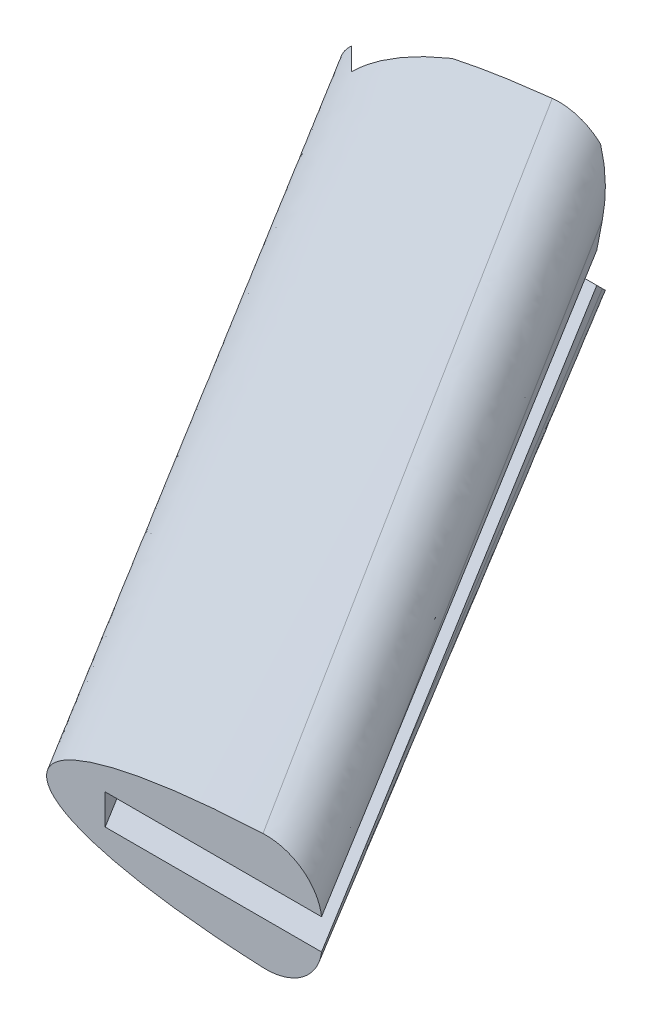
SolidWorks part; units mm, degrees
ref_plane "Front Plane" through (0, 0, 0) normal (0, 0, 1) x (1, 0, 0)
ref_plane "Top Plane" through (0, 0, 0) normal (0, 1, 0) x (1, 0, 0)
ref_plane "Right Plane" through (0, 0, 0) normal (1, 0, 0) x (0, 0, -1)
ref_plane "Plane1" through (0, 0, 82.55) normal (0, 0, 1) x (1, 0, 0)
curve "Curve1"
  spline degree 3 poles (25.4, 0.032, 0) (25.3951, 0.0327, 0) (25.3753, 0.0355, 0) (25.3309, 0.0417, 0) (25.257, 0.052, 0) (25.1537, 0.0664, 0) (25.0214, 0.0846, 0) (24.8603, 0.1068, 0) (24.6708, 0.1326, 0) (24.4533, 0.1619, 0) (24.2084, 0.1946, 0) (23.9366, 0.2304, 0) (23.6385, 0.2691, 0) (23.3149, 0.3106, 0) (22.9666, 0.3545, 0) (22.5942, 0.4008, 0) (22.1987, 0.449, 0) (21.7811, 0.499, 0) (21.3422, 0.5505, 0) (20.8832, 0.6032, 0) (20.405, 0.6571, 0) (19.9089, 0.7116, 0) (19.3959, 0.7667, 0) (18.8673, 0.8219, 0) (18.3242, 0.8772, 0) (17.7681, 0.9321, 0) (17.2001, 0.9864, 0) (16.6216, 1.0399, 0) (16.0339, 1.0922, 0) (15.4384, 1.143, 0) (14.8366, 1.1921, 0) (14.2297, 1.2391, 0) (13.6193, 1.2836, 0) (13.0067, 1.3254, 0) (12.3935, 1.3642, 0) (11.7809, 1.3995, 0) (11.1705, 1.4311, 0) (10.5636, 1.4587, 0) (9.9618, 1.4818, 0) (9.3663, 1.5004, 0) (8.7786, 1.514, 0) (8.2001, 1.5224, 0) (7.632, 1.5254, 0) (7.0758, 1.5227, 0) (6.5327, 1.5144, 0) (6.0041, 1.5, 0) (5.491, 1.4798, 0) (4.9948, 1.4535, 0) (4.5166, 1.4212, 0) (4.0575, 1.3829, 0) (3.6185, 1.3388, 0) (3.2008, 1.2888, 0) (2.8052, 1.2334, 0) (2.4327, 1.1725, 0) (2.0841, 1.1064, 0) (1.7603, 1.0355, 0) (1.462, 0.96, 0) (1.1898, 0.8801, 0) (0.9445, 0.7962, 0) (0.7264, 0.7086, 0) (0.536, 0.6175, 0) (0.3737, 0.523, 0) (0.2396, 0.4254, 0) (0.1341, 0.3245, 0) (0.0574, 0.22, 0) (0.0105, 0.1114, 0) (-0.0051, 0, 0) (0.0105, -0.1114, 0) (0.0574, -0.22, 0) (0.1341, -0.3245, 0) (0.2396, -0.4254, 0) (0.3737, -0.523, 0) (0.536, -0.6175, 0) (0.7264, -0.7086, 0) (0.9445, -0.7962, 0) (1.1898, -0.8801, 0) (1.462, -0.96, 0) (1.7603, -1.0355, 0) (2.0841, -1.1064, 0) (2.4327, -1.1725, 0) (2.8052, -1.2334, 0) (3.2008, -1.2888, 0) (3.6185, -1.3388, 0) (4.0575, -1.3829, 0) (4.5166, -1.4212, 0) (4.9948, -1.4535, 0) (5.491, -1.4798, 0) (6.0041, -1.5, 0) (6.5327, -1.5144, 0) (7.0758, -1.5227, 0) (7.632, -1.5254, 0) (8.2001, -1.5224, 0) (8.7786, -1.514, 0) (9.3663, -1.5004, 0) (9.9618, -1.4818, 0) (10.5636, -1.4587, 0) (11.1705, -1.4311, 0) (11.7809, -1.3995, 0) (12.3935, -1.3642, 0) (13.0067, -1.3254, 0) (13.6193, -1.2836, 0) (14.2297, -1.2391, 0) (14.8366, -1.1921, 0) (15.4384, -1.143, 0) (16.0339, -1.0922, 0) (16.6216, -1.0399, 0) (17.2001, -0.9864, 0) (17.7681, -0.9321, 0) (18.3242, -0.8772, 0) (18.8673, -0.8219, 0) (19.3959, -0.7667, 0) (19.9089, -0.7116, 0) (20.405, -0.6571, 0) (20.8832, -0.6032, 0) (21.3422, -0.5505, 0) (21.7811, -0.499, 0) (22.1987, -0.449, 0) (22.5942, -0.4008, 0) (22.9666, -0.3545, 0) (23.3149, -0.3106, 0) (23.6385, -0.2691, 0) (23.9366, -0.2304, 0) (24.2084, -0.1946, 0) (24.4533, -0.1619, 0) (24.6708, -0.1326, 0) (24.8603, -0.1068, 0) (25.0214, -0.0846, 0) (25.1537, -0.0664, 0) (25.257, -0.052, 0) (25.3309, -0.0417, 0) (25.3753, -0.0355, 0) (25.3951, -0.0327, 0) (25.4, -0.032, 0) knots 0 0 0 0 0.000289 0.001156 0.002598 0.004612 0.007194 0.010336 0.014031 0.018272 0.023046 0.028343 0.03415 0.040454 0.047238 0.054489 0.062187 0.070314 0.078852 0.08778 0.097078 0.106722 0.116691 0.126961 0.137507 0.148306 0.159331 0.170556 0.181957 0.193504 0.205171 0.216932 0.228758 0.240621 0.252495 0.26435 0.276161 0.287898 0.299536 0.311047 0.322405 0.333584 0.344559 0.355306 0.3658 0.376018 0.385937 0.395538 0.404798 0.413699 0.422221 0.430349 0.438066 0.445357 0.452209 0.458612 0.464554 0.47003 0.475035 0.479569 0.483637 0.48725 0.490431 0.493219 0.495674 0.497891 0.5 0.502109 0.504326 0.506781 0.509569 0.51275 0.516363 0.520431 0.524965 0.52997 0.535446 0.541388 0.547791 0.554643 0.561934 0.569651 0.577779 0.586301 0.595202 0.604462 0.614063 0.623982 0.6342 0.644694 0.655441 0.666416 0.677595 0.688953 0.700464 0.712102 0.723839 0.73565 0.747505 0.759379 0.771242 0.783068 0.794829 0.806496 0.818043 0.829444 0.840669 0.851694 0.862493 0.873039 0.883309 0.893278 0.902922 0.91222 0.921148 0.929686 0.937813 0.945511 0.952762 0.959546 0.96585 0.971657 0.976954 0.981728 0.985969 0.989664 0.992806 0.995388 0.997402 0.998844 0.999711 1 1 1 1
sketch "Sketch1" plane through (0, 0, 82.55) normal (0, 0, 1) x (1, 0, 0)
  line L0 (158.75, -0.136) -> (158.75, 0.136)
  line L1 (158.75, 0) -> (50.8, 0) construction
  spline S1 degree 3 poles (158.75, 0.136) (158.729, 0.139) (158.645, 0.1508) (158.3098, 0.1976) (157.8081, 0.2677) (157.1408, 0.3597) (156.4561, 0.4539) (155.6507, 0.5636) (154.7264, 0.6881) (153.6855, 0.8269) (152.5304, 0.9791) (151.2638, 1.1439) (149.8885, 1.3199) (147.8475, 1.5775) (145.6729, 1.8449) (143.3696, 2.1206) (141.5045, 2.3396) (139.5535, 2.5638) (137.5214, 2.7925) (135.4127, 3.0242) (133.2325, 3.2583) (130.9859, 3.493) (128.678, 3.728) (126.3143, 3.9613) (123.9003, 4.1924) (121.4416, 4.4195) (118.944, 4.642) (116.4133, 4.8579) (113.8554, 5.0664) (111.2763, 5.2661) (108.682, 5.4554) (106.0786, 5.6331) (103.4722, 5.7978) (100.009, 5.9975) (96.5614, 6.1659) (92.3047, 6.3299) (88.9536, 6.4222) (85.6503, 6.4702) (83.2361, 6.4828) (80.8722, 6.4716) (78.5642, 6.4361) (76.3173, 6.3752) (74.1369, 6.2891) (72.028, 6.1773) (69.9956, 6.0401) (68.0443, 5.8775) (66.1788, 5.6897) (64.4033, 5.4775) (62.7221, 5.2418) (61.1389, 4.983) (59.6575, 4.7024) (58.2813, 4.401) (57.0135, 4.0799) (55.8569, 3.7406) (54.814, 3.384) (53.887, 3.0115) (53.0779, 2.6242) (52.3881, 2.2228) (51.8184, 1.808) (51.37, 1.3792) (51.0439, 0.9351) (50.8445, 0.4736) (50.7783, 0) (50.8445, -0.4736) (51.0439, -0.9351) (51.37, -1.3792) (51.8184, -1.808) (52.3881, -2.2228) (53.0779, -2.6242) (53.887, -3.0115) (54.814, -3.384) (55.8569, -3.7406) (57.0135, -4.0799) (58.2813, -4.401) (59.6575, -4.7024) (61.1389, -4.983) (62.7221, -5.2418) (64.4033, -5.4775) (66.1788, -5.6897) (68.0443, -5.8775) (69.9956, -6.0401) (72.028, -6.1773) (74.1369, -6.2891) (76.3173, -6.3752) (78.5642, -6.4361) (80.8722, -6.4716) (83.2361, -6.4828) (85.6503, -6.4702) (88.9536, -6.4222) (93.1656, -6.3061) (97.4217, -6.1264) (100.8688, -5.9479) (103.4722, -5.7978) (106.0786, -5.6331) (108.682, -5.4554) (111.2763, -5.2661) (113.8554, -5.0664) (116.4133, -4.8579) (118.944, -4.642) (121.4416, -4.4195) (123.9003, -4.1924) (126.3143, -3.9613) (128.678, -3.728) (130.9859, -3.493) (133.2325, -3.2583) (135.4127, -3.0242) (137.5214, -2.7925) (139.5535, -2.5638) (141.5045, -2.3396) (143.3696, -2.1206) (145.6729, -1.8449) (147.8475, -1.5775) (149.8885, -1.3199) (151.2638, -1.1439) (152.5304, -0.9791) (153.6855, -0.8269) (154.7264, -0.6881) (155.6507, -0.5636) (156.4561, -0.4539) (157.1408, -0.3597) (157.8081, -0.2677) (158.3098, -0.1976) (158.645, -0.1508) (158.729, -0.139) (158.75, -0.136) knots 0 0 0 0 0.000289 0.001156 0.004612 0.007194 0.010336 0.014031 0.018272 0.023046 0.028343 0.03415 0.040454 0.047238 0.062187 0.070314 0.078852 0.08778 0.097078 0.106722 0.116691 0.126961 0.137507 0.148306 0.159331 0.170556 0.181957 0.193504 0.205171 0.216932 0.228758 0.240621 0.252495 0.26435 0.287898 0.299536 0.322405 0.333584 0.344559 0.355306 0.3658 0.376018 0.385937 0.395538 0.404798 0.413699 0.422221 0.430349 0.438066 0.445357 0.452209 0.458612 0.464554 0.47003 0.475035 0.479569 0.483637 0.48725 0.490431 0.493219 0.495674 0.497891 0.5 0.502109 0.504326 0.506781 0.509569 0.51275 0.516363 0.520431 0.524965 0.52997 0.535446 0.541388 0.547791 0.554643 0.561934 0.569651 0.577779 0.586301 0.595202 0.604462 0.614063 0.623982 0.6342 0.644694 0.655441 0.666416 0.677595 0.700464 0.723839 0.73565 0.747505 0.759379 0.771242 0.783068 0.794829 0.806496 0.818043 0.829444 0.840669 0.851694 0.862493 0.873039 0.883309 0.893278 0.902922 0.91222 0.921148 0.929686 0.937813 0.952762 0.959546 0.96585 0.971657 0.976954 0.981728 0.985969 0.989664 0.992806 0.995388 0.998844 0.999711 1 1 1 1
  point P2 (0, 0)
  dimension "D1" = 50.8
  dimension "D2" = 107.95
sketch "Sketch2" plane through (0, 0, 0) normal (0, 0, 1) x (1, 0, 0)
  line L0 (158.75, 0.2) -> (158.75, -0.2)
  line L1 (158.75, 0) -> (0, 0) construction
  spline S1 degree 3 poles (158.75, 0.2) (158.7191, 0.2044) (158.5956, 0.2217) (158.1027, 0.2906) (157.3648, 0.3937) (156.3836, 0.529) (155.3767, 0.6675) (154.1922, 0.8288) (152.833, 1.0119) (151.3023, 1.2161) (149.6035, 1.4399) (147.7408, 1.6822) (145.7184, 1.9411) (142.7169, 2.3199) (139.5189, 2.713) (136.1318, 3.1185) (133.389, 3.4406) (130.5199, 3.7702) (127.5314, 4.1066) (124.4304, 4.4474) (121.2243, 4.7916) (117.9204, 5.1368) (114.5265, 5.4823) (111.0504, 5.8255) (107.5004, 6.1653) (103.8848, 6.4993) (100.2118, 6.8264) (96.4902, 7.144) (92.7286, 7.4506) (88.9358, 7.7443) (85.1206, 8.0227) (81.2921, 8.284) (77.4592, 8.5262) (72.3662, 8.8198) (67.2961, 9.0676) (61.0363, 9.3086) (56.1082, 9.4444) (51.2504, 9.5149) (47.7001, 9.5335) (44.2239, 9.5171) (40.8297, 9.4649) (37.5255, 9.3753) (34.319, 9.2487) (31.2177, 9.0843) (28.2288, 8.8825) (25.3593, 8.6433) (22.6158, 8.3672) (20.0049, 8.0552) (17.5324, 7.7086) (15.2043, 7.328) (13.0258, 6.9153) (11.0019, 6.4721) (9.1375, 5.9999) (7.4366, 5.5008) (5.9029, 4.9765) (4.5397, 4.4287) (3.3498, 3.8591) (2.3354, 3.2688) (1.4977, 2.6588) (0.8382, 2.0282) (0.3587, 1.3751) (0.0655, 0.6964) (-0.0319, 0) (0.0655, -0.6964) (0.3587, -1.3751) (0.8382, -2.0282) (1.4977, -2.6588) (2.3354, -3.2688) (3.3498, -3.8591) (4.5397, -4.4287) (5.9029, -4.9765) (7.4366, -5.5008) (9.1375, -5.9999) (11.0019, -6.4721) (13.0258, -6.9153) (15.2043, -7.328) (17.5324, -7.7086) (20.0049, -8.0552) (22.6158, -8.3672) (25.3593, -8.6433) (28.2288, -8.8825) (31.2177, -9.0843) (34.319, -9.2487) (37.5255, -9.3753) (40.8297, -9.4649) (44.2239, -9.5171) (47.7001, -9.5335) (51.2504, -9.5149) (56.1082, -9.4444) (62.3024, -9.2737) (68.5614, -9.0094) (73.6306, -8.7469) (77.4592, -8.5262) (81.2921, -8.284) (85.1206, -8.0227) (88.9358, -7.7443) (92.7286, -7.4506) (96.4902, -7.144) (100.2118, -6.8264) (103.8848, -6.4993) (107.5004, -6.1653) (111.0504, -5.8255) (114.5265, -5.4823) (117.9204, -5.1368) (121.2243, -4.7916) (124.4304, -4.4474) (127.5314, -4.1066) (130.5199, -3.7702) (133.389, -3.4406) (136.1318, -3.1185) (139.5189, -2.713) (142.7169, -2.3199) (145.7184, -1.9411) (147.7408, -1.6822) (149.6035, -1.4399) (151.3023, -1.2161) (152.833, -1.0119) (154.1922, -0.8288) (155.3767, -0.6675) (156.3836, -0.529) (157.3648, -0.3937) (158.1027, -0.2906) (158.5956, -0.2217) (158.7191, -0.2044) (158.75, -0.2) knots 0 0 0 0 0.000289 0.001156 0.004612 0.007194 0.010336 0.014031 0.018272 0.023046 0.028343 0.03415 0.040454 0.047238 0.062187 0.070314 0.078852 0.08778 0.097078 0.106722 0.116691 0.126961 0.137507 0.148306 0.159331 0.170556 0.181957 0.193504 0.205171 0.216932 0.228758 0.240621 0.252495 0.26435 0.287898 0.299536 0.322405 0.333584 0.344559 0.355306 0.3658 0.376018 0.385937 0.395538 0.404798 0.413699 0.422221 0.430349 0.438066 0.445357 0.452209 0.458612 0.464554 0.47003 0.475035 0.479569 0.483637 0.48725 0.490431 0.493219 0.495674 0.497891 0.5 0.502109 0.504326 0.506781 0.509569 0.51275 0.516363 0.520431 0.524965 0.52997 0.535446 0.541388 0.547791 0.554643 0.561934 0.569651 0.577779 0.586301 0.595202 0.604462 0.614063 0.623982 0.6342 0.644694 0.655441 0.666416 0.677595 0.700464 0.723839 0.73565 0.747505 0.759379 0.771242 0.783068 0.794829 0.806496 0.818043 0.829444 0.840669 0.851694 0.862493 0.873039 0.883309 0.893278 0.902922 0.91222 0.921148 0.929686 0.937813 0.952762 0.959546 0.96585 0.971657 0.976954 0.981728 0.985969 0.989664 0.992806 0.995388 0.998844 0.999711 1 1 1 1
  dimension "D1" = 158.75
loft "Loft1" add profiles "Sketch2", "Sketch1"
sketch "Sketch3" plane through (0, 0, 0) normal (0, 1, 0) x (1, 0, 0)
  line L0 (158.75, 0) -> (6.35, 0)
  line L1 (158.75, 0) -> (0, 0) construction
  line L2 (6.35, 0) -> (57.15, -82.55)
  line L3 (50.8, -82.55) -> (158.75, -82.55) construction
  line L4 (57.15, -82.55) -> (158.75, -82.55)
  line L5 (158.75, -82.55) -> (158.75, 0)
  dimension "D1" = 152.4
  dimension "D2" = 101.6
extrude "Cut-Extrude1" cut sketch "Sketch3" against normal mid plane 3.302
sketch "Sketch4" plane through (0, 0, 0) normal (0, 1, 0) x (1, 0, 0)
  line L1 (140.357, 0) -> (147.977, 0)
  line L2 (140.357, 0) -> (140.357, -82.55)
  line L3 (140.357, -82.55) -> (147.977, -82.55)
  line L4 (147.977, 0) -> (147.977, -82.55)
  dimension "D1" = 7.62
extrude "Cut-Extrude2" cut sketch "Sketch4" against normal through all both and the other way through all
chamfer "Chamfer1" distance 5.08 angle 45 3 edges at (6.35, 0, 0)
sketch "Sketch5" plane through (0, 0, 0) normal (0, 1, 0) x (1, 0, 0)
  line L0 (29.8242, 0) -> (80.6242, -82.55)
  line L1 (101.2732, 0) -> (12.1976, 0) construction
  line L2 (50.8, -82.55) -> (140.357, -82.55) construction
  line L3 (80.6242, -82.55) -> (140.357, -82.55)
  line L4 (140.357, -82.55) -> (140.357, 0)
  line L5 (140.357, 0) -> (29.8242, 0)
  line L6 (0, 0) -> (50.8, -82.55) construction
  point P6 (76.739, -82.55)
  dimension "D1" = 25.4
extrude "Cut-Extrude3" cut sketch "Sketch5" against normal through all both and the other way through all
fillet "Fillet1" radius 5.08 2 edges at (49.3212, 8.0935, 31.6827) (68.3916, -7.1347, 62.672)
